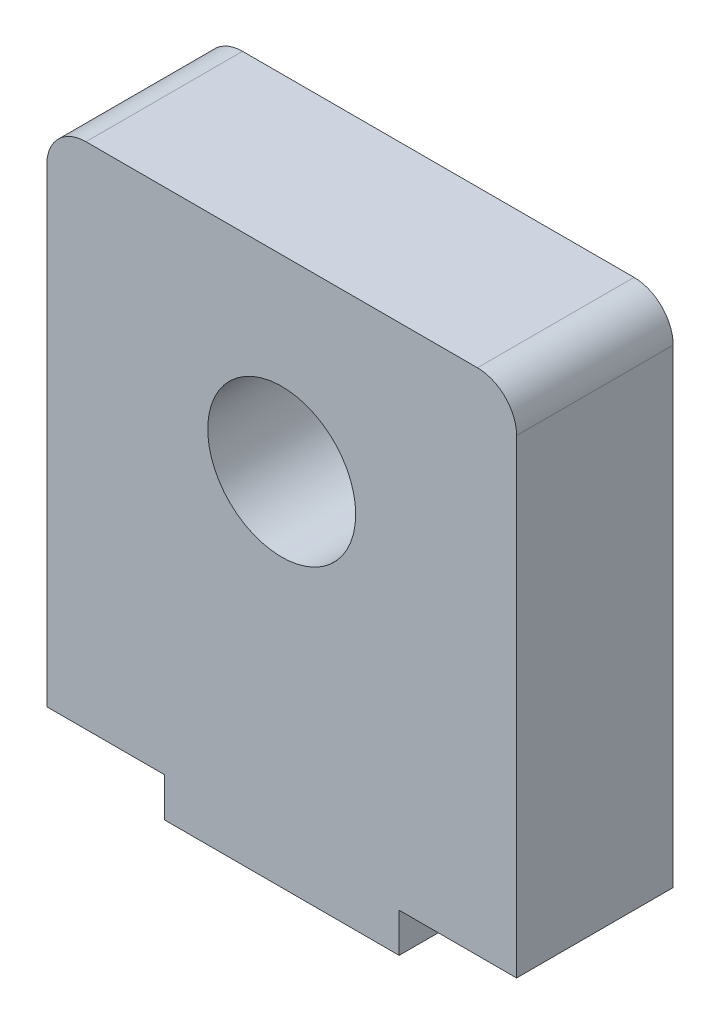
SolidWorks part; units mm, degrees
material "6061-T6 (SS)"
ref_plane "X-Y Datum" through (0, 0, 0) normal (0, 0, 1) x (1, 0, 0)
ref_plane "X-Z Datum" through (0, 0, 0) normal (0, 1, 0) x (1, 0, 0)
ref_plane "Y-Z Datum" through (0, 0, 0) normal (1, 0, 0) x (0, 0, -1)
sketch "Sketch1" plane through (0, 0, 0) normal (0, 0, 1) x (1, 0, 0)
  line L0 (0, 11.1125) -> (0, -11.1125) construction
  line L5 (-9.525, 11.1125) -> (9.525, 11.1125)
  line L6 (-9.525, 11.1125) -> (-9.525, -11.1125)
  line L7 (-9.525, -11.1125) -> (9.525, -11.1125)
  line L8 (9.525, 11.1125) -> (9.525, -11.1125)
  line L9 (-9.525, 11.1125) -> (9.525, -11.1125) construction
  line L10 (-9.525, -11.1125) -> (9.525, 11.1125) construction
  line L11 (-9.525, -9.525) -> (9.525, -9.525)
  line L12 (0, -9.525) -> (0, -11.1125) construction
  line L14 (-4.7625, -9.525) -> (4.7625, -9.525)
  line L15 (-4.7625, -9.525) -> (-4.7625, -11.1125)
  line L16 (-4.7625, -11.1125) -> (4.7625, -11.1125)
  line L17 (4.7625, -9.525) -> (4.7625, -11.1125)
  line L18 (-4.7625, -9.525) -> (4.7625, -11.1125) construction
  line L19 (-4.7625, -11.1125) -> (4.7625, -9.525) construction
  circle A0 centre (0, 3.4925) radius 3
  point P0 (0, 0)
  point P14 (0, -10.3188)
  dimension "D2" = 6
  dimension "D1" = 19.05
  dimension "D3" = 22.225
  dimension "D4" = 7.62
  dimension "D5" = 1.5875
  dimension "D6" = 9.525
extrude "Boss-Extrude1" add sketch "Sketch1" along normal blind 6.35 contours L6 L11 L8 L5 A0 | L17 L11 L15 L7 region at (0, 10.8316, 0) region at (0, -10.3188, 0)
fillet "Fillet1" radius 1.5875 2 edges at (9.525, 11.1125, 3.175) (-9.525, 11.1125, 3.175)
